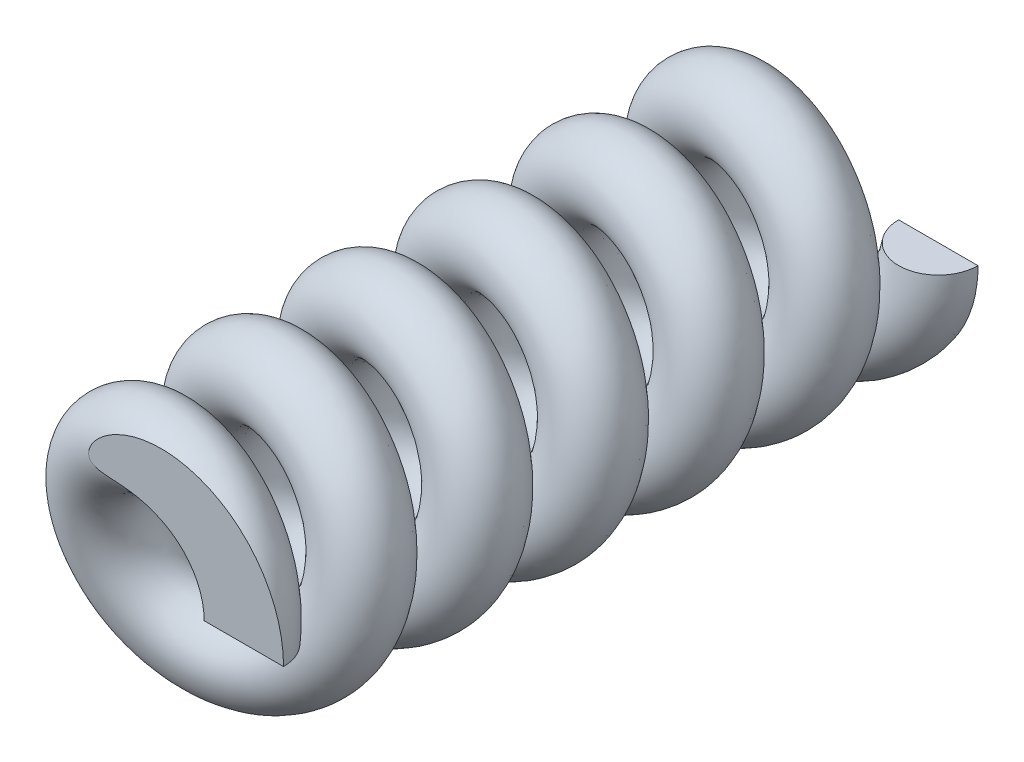
SolidWorks part; units mm, degrees
material "1023 Arkusz stali węglowej (SS)"
ref_plane "Płaszczyzna przednia" through (0, 0, 0) normal (0, 0, 1) x (1, 0, 0)
ref_plane "Płaszczyzna górna" through (0, 0, 0) normal (0, 1, 0) x (1, 0, 0)
ref_plane "Płaszczyzna prawa" through (0, 0, 0) normal (1, 0, 0) x (0, 0, -1)
sketch "Szkic1" plane through (0, 0, 0) normal (0, 0, 1) x (1, 0, 0)
  circle A0 centre (0, 0) radius 2.5
  dimension "D1" = 5
curve "Helisa/Spirala1" pitch 2.9167 height 17.5 radius 2.5 left hand yes centre (0, 0, 0) axis (0, 0, 1) start towards (1, 0, 0)
ref_plane "Płaszczyzna1" through (0, 0, 17.5) normal (0, 0, 1) x (1, 0, 0)
sketch "Szkic2" plane through (0, 0, 0) normal (0, 1, 0) x (1, 0, 0)
  circle A0 centre (2.5, 0) radius 1
  dimension "D1" = 2
sweep "Wyciągnięcie po ścieżce1" add profiles "Szkic2" path "Helisa/Spirala1"
other "Cięcie powierzchnią1"
other "Cięcie powierzchnią2" flip cut yes
